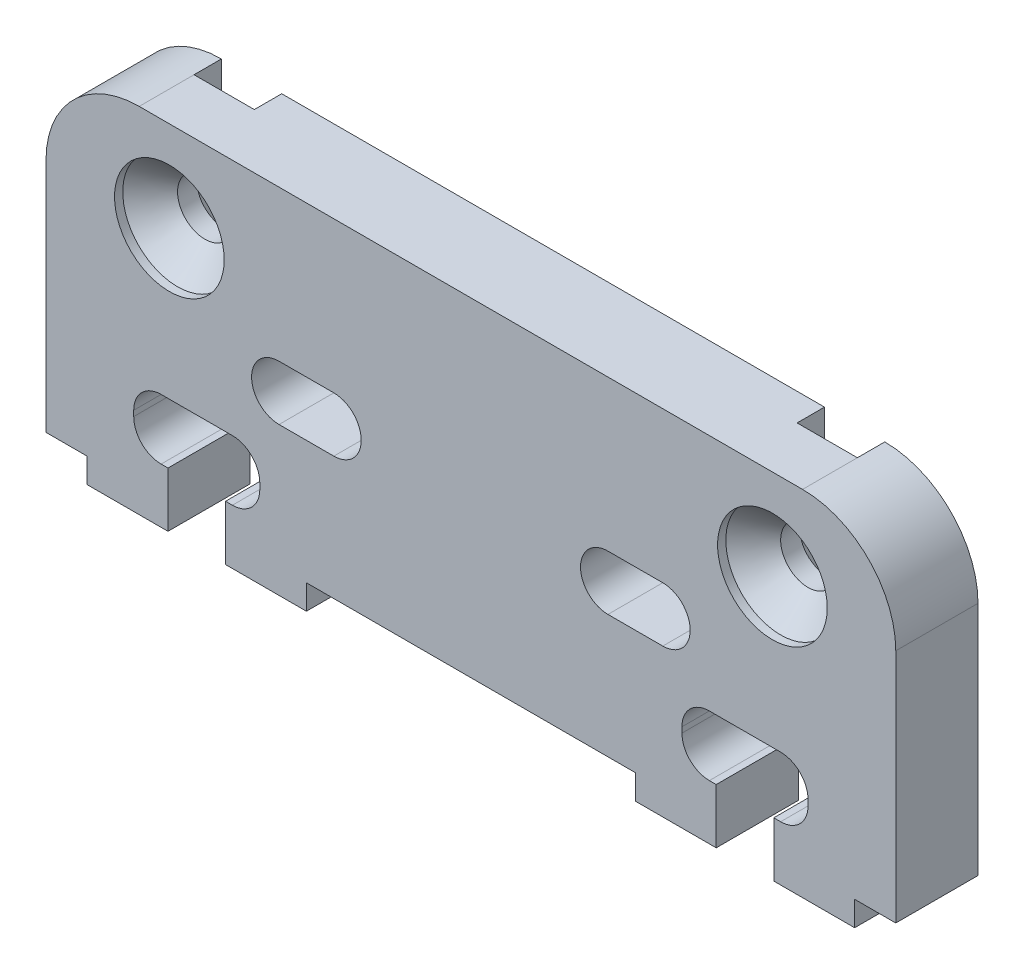
SolidWorks part; units mm, degrees
ref_plane "Front Plane" through (0, 0, 0) normal (0, 0, 1) x (1, 0, 0)
ref_plane "Top Plane" through (0, 0, 0) normal (0, 1, 0) x (1, 0, 0)
ref_plane "Right Plane" through (0, 0, 0) normal (1, 0, 0) x (0, 0, -1)
sketch "Sketch1" plane through (0, 0, 0) normal (0, 0, 1) x (1, 0, 0)
  line L0 (-10, -6.9) -> (-10, 6) construction
  line L1 (-15.5, 6) -> (15.5, 6)
  line L2 (-15.5, 6) -> (-15.5, -6)
  line L3 (-15.5, -6) -> (15.5, -6)
  line L4 (15.5, 6) -> (15.5, -6)
  line L5 (-15.5, 6) -> (15.5, -6) construction
  line L6 (-15.5, -6) -> (15.5, 6) construction
  line L7 (-15.5, -6) -> (-6, -6)
  line L9 (-14, -6.9) -> (-6, -6.9)
  line L10 (-6, -6) -> (-6, -6.9)
  line L11 (0, 6) -> (0, -6) construction
  line L12 (-11.05, -4.9) -> (-8.95, -4.9)
  line L13 (-11.05, -4.9) -> (-11.05, -6.9)
  line L14 (-11.05, -6.9) -> (-8.95, -6.9)
  line L15 (-8.95, -4.9) -> (-8.95, -6.9)
  line L16 (-11.05, -4.9) -> (-8.95, -6.9) construction
  line L17 (-11.05, -6.9) -> (-8.95, -4.9) construction
  line L18 (-12.3, -2.7) -> (-7.7, -2.7)
  line L19 (-12.3, -2.7) -> (-12.3, -4.9)
  line L20 (-12.3, -4.9) -> (-7.7, -4.9)
  line L21 (-7.7, -2.7) -> (-7.7, -4.9)
  line L22 (-12.3, -2.7) -> (-7.7, -4.9) construction
  line L23 (-12.3, -4.9) -> (-7.7, -2.7) construction
  line L24 (12.3, -2.7) -> (7.7, -2.7)
  line L25 (12.3, -2.7) -> (12.3, -4.9)
  line L26 (12.3, -4.9) -> (7.7, -4.9)
  line L27 (7.7, -2.7) -> (7.7, -4.9)
  line L28 (11.05, -4.9) -> (8.95, -4.9)
  line L29 (11.05, -4.9) -> (11.05, -6.9)
  line L30 (11.05, -6.9) -> (8.95, -6.9)
  line L31 (8.95, -4.9) -> (8.95, -6.9)
  line L32 (15.5, -6) -> (6, -6)
  line L33 (6, -6) -> (6, -6.9)
  line L34 (14, -6.9) -> (6, -6.9)
  line L36 (-14, -6.9) -> (-14, -6)
  line L37 (14, -6.9) -> (14, -6)
  line L38 (10, -2.7) -> (10, -6.9) construction
  line L39 (7, -0.5) -> (5, -0.5) construction
  line L40 (7, -1.5) -> (5, -1.5)
  line L41 (7, 0.5) -> (5, 0.5)
  line L42 (-7, -0.5) -> (-5, -0.5) construction
  line L43 (-7, -1.5) -> (-5, -1.5)
  line L44 (-7, 0.5) -> (-5, 0.5)
  arc A0 (7, -1.5) -> (7, 0.5) centre (7, -0.5) ccw
  arc A1 (5, 0.5) -> (5, -1.5) centre (5, -0.5) ccw
  arc A2 (-7, -1.5) -> (-7, 0.5) centre (-7, -0.5) cw
  arc A3 (-5, 0.5) -> (-5, -1.5) centre (-5, -0.5) cw
  point P0 (0, 0)
  point P11 (-10, -5.9)
  point P16 (-10, -3.8)
  point P40 (6, -0.5)
  point P47 (-6, -0.5)
  dimension "D1" = 31
  dimension "D2" = 12
  dimension "D3" = 0.9
  dimension "D4" = 8
  dimension "D5" = 2.1
  dimension "D6" = 2
  dimension "D7" = 2.2
  dimension "D8" = 4.6
  dimension "D9" = 20
  dimension "D10" = 2
  dimension "D11" = 2
  dimension "D12" = 12
  dimension "D13" = 5.5
extrude "Base shape" add sketch "Sketch1" along normal blind 3 contours L31 L26 L27 L24 L25 L29 L3 L4 L1 L2 L13 L20 L19 L18 L21 L15 | L3 L15 L9 L10 | L13 L3 L9 | L34 L31 L3 L33 | L3 L29 L34 region at (0, 0.3282, 0) region at (-12.525, -6.45, 0) region at (12.525, -6.45, 0) region at (-7.475, -6.45, 0) region at (7.475, -6.45, 0)
fillet "Edge radiuses" radius 3.4 2 edges at (15.5, 6, 1.5) (-15.5, 6, 1.5)
sketch "Sketch2" plane through (0, 0, 0) normal (0, 0, -1) x (-1, 0, 0)
  line L0 (0, 6) -> (0, -6) construction
  line L10 (12.1, 6) -> (-12.1, 6) construction
  line L11 (6, -6) -> (-6, -6) construction
  line L16 (-14, -6) -> (-15.5, -6) construction
  line L17 (-12.1, 6.1) -> (-9.9, 6.1)
  line L18 (-12.1, 6.1) -> (-12.1, 0.3)
  line L19 (-11.1, -0.7) -> (-10.9, -0.7)
  line L20 (-9.9, 6.1) -> (-9.9, 0.3)
  line L21 (-12.1, 6.1) -> (-9.9, -0.7) construction
  line L22 (-12.1, -0.7) -> (-9.9, 6.1) construction
  line L23 (12.1, 6.1) -> (9.9, 6.1)
  line L24 (12.1, 6.1) -> (12.1, 0.3)
  line L25 (11.1, -0.7) -> (10.9, -0.7)
  line L26 (9.9, 6.1) -> (9.9, 0.3)
  arc A8 (-10.9, -0.7) -> (-9.9, 0.3) centre (-10.9, 0.3) ccw
  arc A9 (-12.1, 0.3) -> (-11.1, -0.7) centre (-11.1, 0.3) ccw
  arc A10 (12.1, 0.3) -> (11.1, -0.7) centre (11.1, 0.3) cw
  arc A11 (10.9, -0.7) -> (9.9, 0.3) centre (10.9, 0.3) cw
  point P6 (-11, 2.7)
  dimension "D5" = 1
  dimension "D1" = 6.8
  dimension "D2" = 2.2
  dimension "D3" = 22
  dimension "D4" = 8.7
extrude "Camera mount pockets" cut sketch "Sketch2" against normal blind 1
sketch "Sketch3" plane through (0, 0, 1) normal (0, 0, -1) x (-1, 0, 0)
  line L3 (0, 6) -> (0, -6) construction
  line L5 (6, -6) -> (-6, -6) construction
  line L6 (-11.1, -0.7) -> (-10.9, -0.7) construction
  line L7 (-12.1, 6.1) -> (-9.9, 6.1)
  line L8 (-12.1, 6.1) -> (-12.1, -0.7)
  line L9 (-12.1, -0.7) -> (-9.9, -0.7)
  line L10 (-9.9, 6.1) -> (-9.9, -0.7)
  line L11 (-12.1, 6.1) -> (-9.9, -0.7) construction
  line L12 (-12.1, -0.7) -> (-9.9, 6.1) construction
  line L13 (-12.1, 6) -> (-12.1, 0.3) construction
  circle A0 centre (-11, 2.7) radius 1
  circle A1 centre (11, 2.7) radius 1
  point P2 (-11, 2.7)
  point P17 (-11, -0.7)
  point P18 (-11, -0.7)
  dimension "D1" = 2
  dimension "D2" = 6.8
extrude "Camera mount holes" cut sketch "Sketch3" against normal up to next contours A0 | A1 region at (11, 2.7, 1) region at (-11, 2.7, 1)
hole_wizard "CSK for M2 Flat Head Machine Screw1" positions "Sketch4" profile "Sketch5" countersink size "M2" standard "ANSI Metric" end condition through all
sketch "Sketch4" plane through (0, 0, 3) normal (0, 0, 1) x (1, 0, 0)
  point P0 (-11, 2.7)
  point P3 (11, 2.7)
sketch "Sketch5" plane through (-11, 2.7, 3) normal (1, 0, 0) x (0, -1, 0)
  line L0 (0, 0) -> (0, 3)
  line L1 (0, 3) -> (1, 3)
  line L2 (1, 3) -> (1, 1.3)
  line L3 (1, 1.3) -> (2, 0.3)
  line L4 (2, 0.3) -> (2, 0)
  line L6 (2, 0) -> (0, 0)
  line L7 (-1, 1.3) -> (-2, 0.3) construction
  line L11 (0, -6.35) -> (0, 107.95) construction
  dimension "Thru Hole Dia." = 2
  dimension "Thru Hole Depth" = 3
  dimension "C'Sink Dia." = 4
  dimension "C'Sink Angle" = 90
  dimension "Head Clearance" = 0.3
fillet "1mm milling radiuses" radius 1 8 edges at (-7.7, -2.7, 1.5) (-7.7, -4.9, 1.5) (12.3, -4.9, 1.5) (12.3, -2.7, 1.5) (7.7, -2.7, 1.5) (7.7, -4.9, 1.5) (-12.3, -4.9, 1.5) (-12.3, -2.7, 1.5)
sketch "Sketch7" plane through (0, -6.9, 0) normal (0, -1, 0) x (1, 0, 0)
  line L0 (-11.05, 3) -> (-8.95, 0) construction
  line L1 (7, 0) -> (13, 0)
  line L36 (0, 3) -> (0, 0) construction
  line L37 (-6, 3) -> (6, 3) construction
  line L38 (-6, 0) -> (6, 0) construction
  line L39 (-7, 3) -> (-13, 3)
  line L42 (-6, 2) -> (-6, 1)
  line L43 (-7, 0) -> (-13, 0)
  line L44 (-14, 2) -> (-14, 1)
  line L45 (-6, 3) -> (-14, 0) construction
  line L46 (-6, 0) -> (-14, 3) construction
  line L47 (6, 2) -> (6, 1)
  line L48 (7, 3) -> (13, 3)
  line L49 (14, 2) -> (14, 1)
  line L54 (-8.95, 0) -> (-6, 0)
  line L55 (-6, 0) -> (-6, 3)
  line L56 (-6, 3) -> (-8.95, 3)
  line L57 (-8.95, 3) -> (-8.95, 0)
  line L58 (-8.95, 0) -> (-6, 0)
  line L59 (-6, 0) -> (-6, 3)
  line L60 (-6, 3) -> (-8.95, 3)
  line L61 (-8.95, 3) -> (-8.95, 0)
  line L62 (-14, 0) -> (-11.05, 0)
  line L63 (-11.05, 0) -> (-11.05, 3)
  line L64 (-11.05, 3) -> (-14, 3)
  line L65 (-14, 3) -> (-14, 0)
  line L66 (-14, 0) -> (-11.05, 0)
  line L67 (-11.05, 0) -> (-11.05, 3)
  line L68 (-11.05, 3) -> (-14, 3)
  line L69 (-14, 3) -> (-14, 0)
  line L70 (6, 0) -> (8.95, 0)
  line L71 (8.95, 0) -> (8.95, 3)
  line L72 (8.95, 3) -> (6, 3)
  line L73 (6, 3) -> (6, 0)
  line L74 (6, 0) -> (8.95, 0)
  line L75 (8.95, 0) -> (8.95, 3)
  line L76 (8.95, 3) -> (6, 3)
  line L77 (6, 3) -> (6, 0)
  line L78 (11.05, 0) -> (14, 0)
  line L79 (14, 0) -> (14, 3)
  line L80 (14, 3) -> (11.05, 3)
  line L81 (11.05, 3) -> (11.05, 0)
  line L82 (11.05, 0) -> (14, 0)
  line L83 (14, 0) -> (14, 3)
  line L84 (14, 3) -> (11.05, 3)
  line L85 (11.05, 3) -> (11.05, 0)
  arc A4 (-6, 1) -> (-7, 0) centre (-7, 1) cw
  arc A5 (-7, 3) -> (-6, 2) centre (-7, 2) cw
  arc A6 (-13, 0) -> (-14, 1) centre (-13, 1) cw
  arc A7 (-13, 3) -> (-14, 2) centre (-13, 2) ccw
  arc A8 (6, 1) -> (7, 0) centre (7, 1) ccw
  arc A9 (7, 3) -> (6, 2) centre (7, 2) ccw
  arc A10 (13, 3) -> (14, 2) centre (13, 2) cw
  arc A11 (13, 0) -> (14, 1) centre (13, 1) ccw
  point P4 (-10, 1.5)
  dimension "D1" = 1
  dimension "D2" = 0
  dimension "D3" = 0
  dimension "D4" = 0
  dimension "D5" = 0
extrude "Top plate pocket radiuses" [suppressed] cut sketch "Sketch7" against normal up to surface (0.9 mm away) up to face at (14.75, -6, 1.5)
